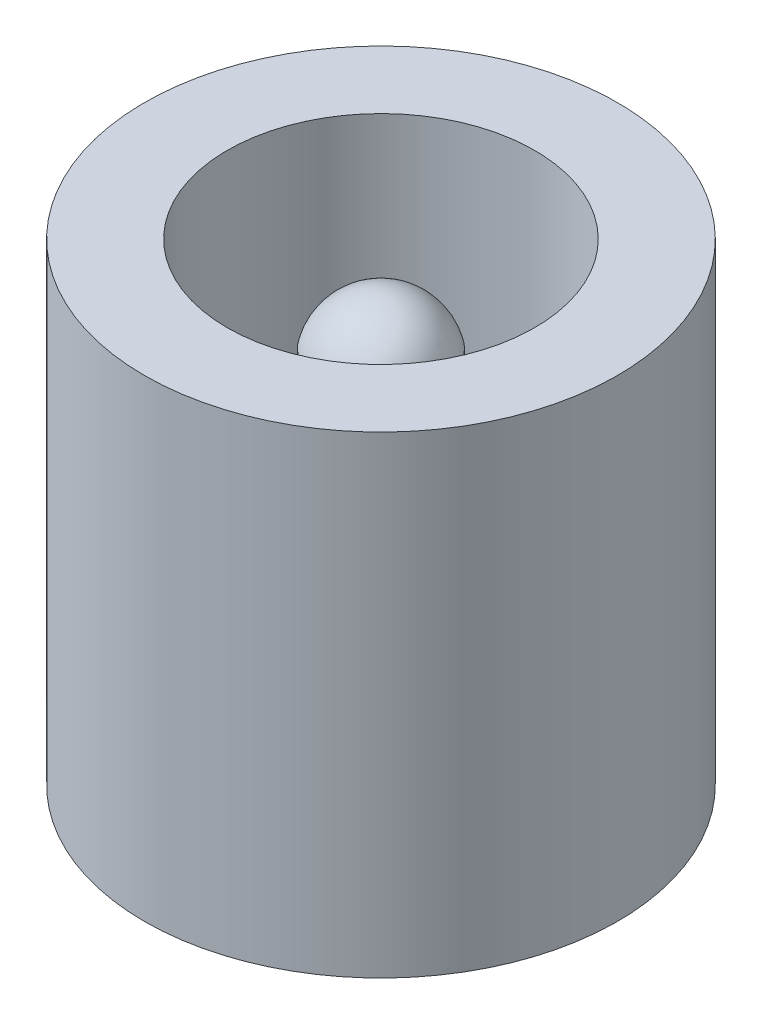
SolidWorks part; units mm, degrees
ref_plane "Front Plane" through (0, 0, 0) normal (0, 0, 1) x (1, 0, 0)
ref_plane "Top Plane" through (0, 0, 0) normal (0, 1, 0) x (1, 0, 0)
ref_plane "Right Plane" through (0, 0, 0) normal (1, 0, 0) x (0, 0, -1)
sketch "Sketch1" plane through (0, 0, 0) normal (0, 1, 0) x (1, 0, 0)
  circle A0 centre (0, 0) radius 5
  dimension "D1" = 10
extrude "Boss-Extrude1" add sketch "Sketch1" along normal blind 10
sketch "Sketch2" plane through (0, 10, 0) normal (0, 1, 0) x (1, 0, 0)
  circle A0 centre (0, 0) radius 3.25
  dimension "D1" = 6.5
extrude "Cut-Extrude1" cut sketch "Sketch2" against normal blind 8
sketch "Sketch3" plane through (0, 2, 0) normal (0, 1, 0) x (1, 0, 0)
  circle A0 centre (0, 0) radius 1.25
  dimension "D1" = 2.5
extrude "Boss-Extrude2" add sketch "Sketch3" along normal blind 6
dome "Dome1" faces to dome 1 distance 1 reverse direction no elliptical dome no face at (0, 8, 1.25) parameters "D1"=1
